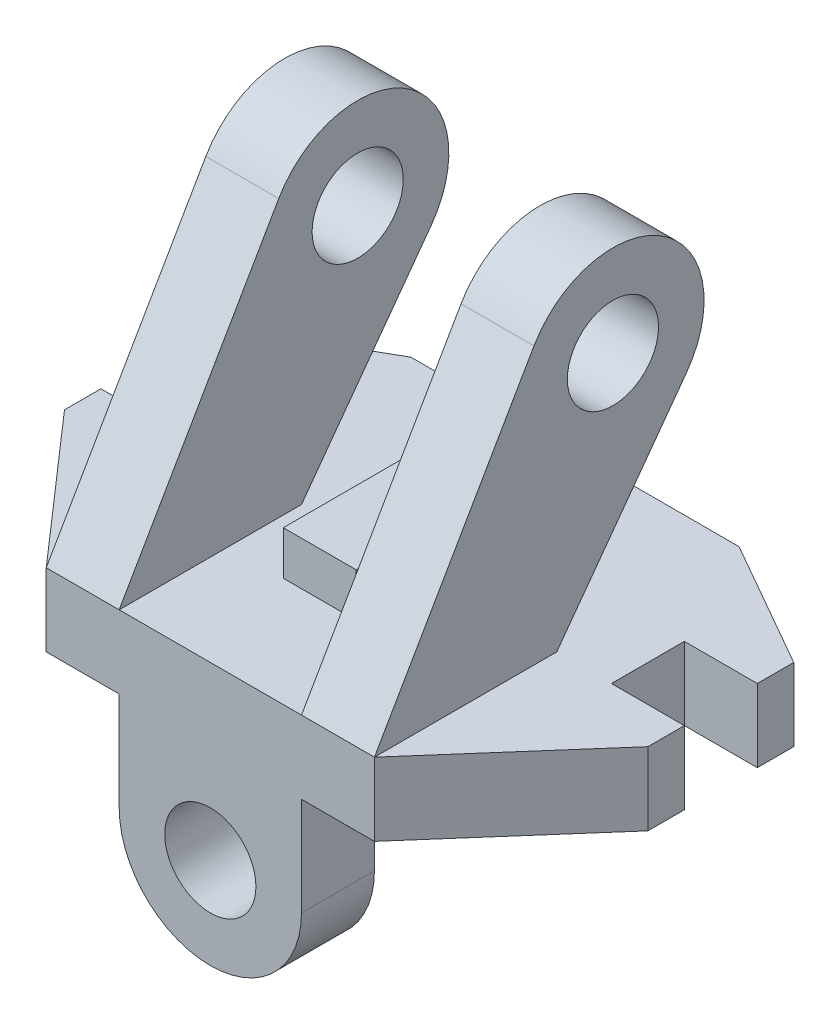
SolidWorks part; units mm, degrees
ref_plane "Front Plane" through (0, 0, 0) normal (0, 0, 1) x (1, 0, 0)
ref_plane "Top Plane" through (0, 0, 0) normal (0, 1, 0) x (1, 0, 0)
ref_plane "Right Plane" through (0, 0, 0) normal (1, 0, 0) x (0, 0, -1)
sketch "Sketch1" plane through (0, 0, 0) normal (0, 0, 1) x (1, 0, 0)
  line L0 (80, 0) -> (80, 156.2143) construction
  line L1 (0, 0) -> (160, 0)
  line L2 (0, 0) -> (0, 20)
  line L3 (0, 20) -> (35, 20)
  line L4 (160, 0) -> (160, 20)
  line L5 (55, 0) -> (105, 0)
  line L6 (55, 0) -> (55, -27)
  line L8 (105, 0) -> (105, -27)
  line L10 (55, 20) -> (55, 105)
  line L11 (55, 105) -> (35, 105)
  line L12 (35, 20) -> (35, 105)
  line L13 (80, 0) -> (80, -27) construction
  line L14 (105, 105) -> (125, 105)
  line L15 (105, 20) -> (105, 105)
  line L16 (125, 20) -> (125, 105)
  line L17 (55, 20) -> (105, 20)
  line L18 (125, 20) -> (160, 20)
  line L19 (70, 32) -> (90, 32)
  line L20 (90, 32) -> (90, 20)
  line L21 (70, 32) -> (70, 20)
  line L22 (34.0106, 80) -> (125, 80) construction
  line L23 (35, 20) -> (55, 20)
  line L24 (105, 20) -> (125, 20)
  arc A0 (55, -27) -> (105, -27) centre (80, -27) ccw
  circle A1 centre (80, -27) radius 12.5
  point P24 (80, 32)
  dimension "D7" = 25
  dimension "D8" = 50
  dimension "D1" = 55
  dimension "D2" = 160
  dimension "D3" = 27
  dimension "D4" = 35
  dimension "D5" = 85
  dimension "D6" = 27
  dimension "D9" = 20
  dimension "D10" = 20
  dimension "D11" = 12
  dimension "D12" = 20
  dimension "D13" = 60
extrude "Boss-Extrude1" add sketch "Sketch1" against normal blind 100 contours L24 L17 L23 L3 L2 L1 L4 L18 region at (80, 10, 0)
extrude "Boss-Extrude2" add sketch "Sketch1<3>" against normal blind 20 contours L6 A0 L8 L1 A1 region at (80, -0.7214, 0)
sketch "Sketch1<3>" plane through (0, 0, 0) normal (0, 0, 1) x (1, 0, 0) same geometry as "Sketch1"
extrude "Boss-Extrude3" add sketch "Sketch1<4>" along normal blind 70 from surface contours L19 L21 L17 L20 region at (80, 26, 0) starting at face at (80, 10, -100)
sketch "Sketch1<4>" plane through (0, 0, 0) normal (0, 0, 1) x (1, 0, 0) same geometry as "Sketch1"
sketch "Sketch2" plane through (0, 0, 0) normal (-1, 0, 0) x (0, 0, 1)
  line L0 (-43.7584, 95.7918) -> (0, 20)
  line L1 (0, 20) -> (-100, 20)
  line L2 (-85.5698, 68.5085) -> (-50, 20)
  arc A0 (-43.7584, 95.7918) -> (-85.5698, 68.5085) centre (-65.409, 83.2918) ccw
  circle A1 centre (-65.409, 83.2918) radius 12.5
  line M11 (0, 20) -> (-100, 20)
  dimension "D4" = 50
  dimension "D5" = 25
  dimension "D1" = 50
  dimension "D2" = 60
extrude "Boss-Extrude4" add sketch "Sketch2" along normal blind 20 from vertex contours L0 A0 L2 A1 M11 region at (0, 58.971, -48.3345) starting at point (55, 0, 0)
extrude "Boss-Extrude5" add sketch "Sketch2<3>" against normal blind 20 from vertex contours L0 A0 L2 A1 M11 region at (0, 58.971, -48.3345) starting at point (105, 0, 0)
sketch "Sketch2<3>" plane through (0, 0, 0) normal (-1, 0, 0) x (0, 0, 1) same geometry as "Sketch2"
sketch "Sketch4" plane through (0, 20, 0) normal (0, 1, 0) x (1, 0, 0)
  line L0 (35, 0) -> (0, 40)
  line L1 (0, 100) -> (0, 0) construction
  line L2 (0, 40) -> (0, 50)
  line L3 (0, 50) -> (20, 50)
  line L4 (20, 50) -> (20, 70)
  line L5 (20, 70) -> (0, 70)
  line L7 (0, 70) -> (0, 80)
  line L8 (0, 80) -> (35, 100)
  line L9 (0, 100) -> (70, 100) construction
  line L10 (80, 100) -> (80, -11.3065) construction
  line L11 (70, 100) -> (90, 100) construction
  line L12 (160, 80) -> (125, 100)
  line L13 (160, 70) -> (160, 80)
  line L14 (140, 70) -> (160, 70)
  line L15 (140, 50) -> (140, 70)
  line L16 (160, 50) -> (140, 50)
  line L17 (160, 40) -> (160, 50)
  line L18 (125, 0) -> (160, 40)
  line L19 (35, 100) -> (125, 100)
  line L20 (35, 0) -> (125, 0)
  line L22 (0, 100) -> (160, 100)
  line L23 (0, 100) -> (0, 0)
  line L24 (0, 0) -> (160, 0)
  line L25 (160, 100) -> (160, 0)
  line M10 (125, 0) -> (160, 0)
  line M11 (160, 0) -> (160, 100)
  line M12 (160, 100) -> (90, 100)
  line M16 (70, 100) -> (0, 100)
  line M17 (0, 100) -> (0, 0)
  line M18 (0, 0) -> (35, 0)
  dimension "D1" = 40
  dimension "D2" = 20
  dimension "D3" = 10
  dimension "D4" = 20
extrude "Cut-Extrude1" cut sketch "Sketch4" against normal through all both and the other way through all contours L8 M17 M16 | L0 M18 M17 | L18 M10 M11 | L12 M11 M12 | L16 L14 L15 M11 | L4 L5 L3 M17 region at (11.6667, 20, -13.3333) region at (148.3333, 20, -13.3333) region at (10, 20, -60) region at (150, 20, -60) region at (11.6667, 20, -93.3333) region at (148.3333, 20, -93.3333)
